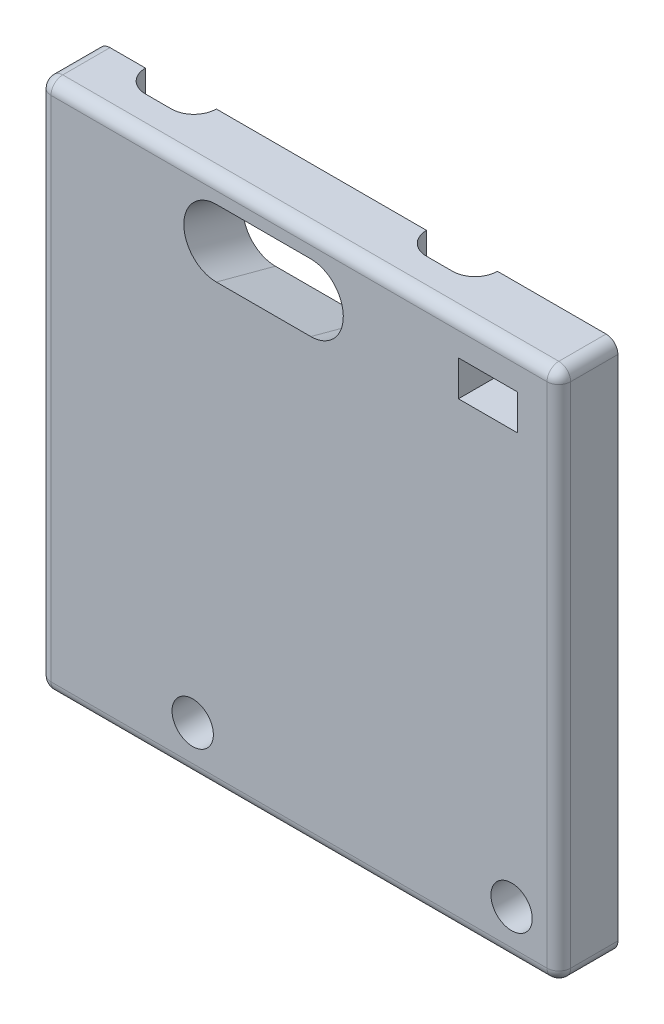
SolidWorks part; units mm, degrees
ref_plane "Front Plane" through (0, 0, 0) normal (0, 0, 1) x (1, 0, 0)
ref_plane "Top Plane" through (0, 0, 0) normal (0, 1, 0) x (1, 0, 0)
ref_plane "Right Plane" through (0, 0, 0) normal (1, 0, 0) x (0, 0, -1)
sketch "Sketch1" plane through (0, 0, 0) normal (0, 0, 1) x (1, 0, 0)
  line L1 (-22, 22.5) -> (22, 22.5)
  line L2 (-22, 22.5) -> (-22, -22.5)
  line L3 (-22, -22.5) -> (22, -22.5)
  line L4 (22, 22.5) -> (22, -22.5)
  line L5 (-22, 22.5) -> (22, -22.5) construction
  line L6 (-22, -22.5) -> (22, 22.5) construction
  point P0 (0, 0)
  dimension "D1" = 44
  dimension "D2" = 45
extrude "Base" add sketch "Sketch1" along normal blind 5
sketch "Sketch2" plane through (0, 22.5, 0) normal (0, 1, 0) x (1, 0, 0)
  line L0 (22, 0) -> (-22, 0) construction
  line L1 (-18, 0) -> (-12, 0)
  line L2 (0, 0) -> (0, -5) construction
  line L3 (22, -5) -> (-22, -5) construction
  line L5 (-16.1, -1.9) -> (-13.9, -1.9)
  line L6 (-18, 0) -> (-18, -5) construction
  line L7 (-3.1, 0) -> (-3.1, -5) construction
  line L8 (9.9, -1.9) -> (7.7, -1.9)
  line L9 (11.8, 0) -> (5.8, 0)
  arc A2 (-16.1, -1.9) -> (-18, 0) centre (-16.1, 0) cw
  arc A3 (-12, 0) -> (-13.9, -1.9) centre (-13.9, 0) cw
  arc A4 (9.9, -1.9) -> (11.8, 0) centre (9.9, 0) ccw
  arc A5 (5.8, 0) -> (7.7, -1.9) centre (7.7, 0) ccw
  point P0 (-15, 0)
  point P15 (-15, -1.9)
  dimension "D1" = 15
  dimension "D2" = 6
  dimension "D3" = 1.9
  dimension "D4" = 11.9
extrude "Wire Grooves" cut sketch "Sketch2" against normal through all
sketch "Sketch4" plane through (0, 0, 0) normal (0, 0, -1) x (-1, 0, 0)
  line L0 (0, 22.5) -> (0, -22.5) construction
  line L3 (-22, 16.5291) -> (22, 16.5291) construction
  line L4 (-22, -22.5) -> (-22, 22.5) construction
  line L5 (22, 22.5) -> (22, -22.5) construction
  line L6 (-22, 22.5) -> (-11.8, 22.5) construction
  line L7 (12, -22.5) -> (-5.8, -22.5) construction
  dimension "D1" = 5.9709
ref_plane "Screw Insertion Hole Reference" through (0, 1.1072, 4.1323) normal (0, -0.2588, -0.9659) x (-1, 0, 0)
sketch "Sketch3" plane through (0, 0.5961, 4.2692) normal (0, -0.2588, -0.9659) x (-1, 0, 0)
  line L0 (0, 0.5291) -> (0, 22.2625) construction
  line L1 (-1, 16.2925) -> (7, 16.2925) construction
  line L2 (-22, 22.2625) -> (-11.8, 22.2625) construction
  line L3 (-1, 19.0425) -> (7, 19.0425)
  line L4 (-1, 13.5425) -> (7, 13.5425)
  line L5 (-5.8, 22.2625) -> (12, 22.2625) construction
  arc A1 (-1, 19.0425) -> (-1, 13.5425) centre (-1, 16.2925) ccw
  arc A2 (7, 13.5425) -> (7, 19.0425) centre (7, 16.2925) ccw
  point P5 (3, 16.2925)
  point P14 (2.458, 16.2925)
  dimension "D1" = 5.97
  dimension "D2" = 2.75
  dimension "D3" = 8
  dimension "D4" = 3
extrude "Screw Insertion Hole" cut sketch "Sketch3" against normal through all both and the other way through all
sketch "Sketch5" plane through (0, 0, 0) normal (0, 0, -1) x (-1, 0, 0)
  line L1 (-22, 22.5) -> (-11.8, 22.5) construction
  line L3 (0, 22.5) -> (0, -22.5) construction
  line L7 (-18.5, 19.5) -> (-13.5, 19.5)
  line L8 (-18.5, 19.5) -> (-18.5, 16.5)
  line L9 (-18.5, 16.5) -> (-13.5, 16.5)
  line L10 (-13.5, 19.5) -> (-13.5, 16.5)
  line L11 (-18.5, 19.5) -> (-13.5, 16.5) construction
  line L12 (-18.5, 16.5) -> (-13.5, 19.5) construction
  line L16 (-22, 22.5) -> (-11.8, 22.5) construction
  line L20 (12, -22.5) -> (-5.8, -22.5) construction
  line L21 (-4, 22.5) -> (-4, -22.5) construction
  line L22 (-5.8, 22.5) -> (12, 22.5) construction
  line L23 (12, -22.5) -> (-5.8, -22.5) construction
  point P12 (-16, 18)
  dimension "D1" = 5
  dimension "D2" = 3
  dimension "D3" = 3
  dimension "D4" = 16
  dimension "D5" = 4
extrude "Zip Tie Slots" cut sketch "Sketch5" against normal through all
sketch "Sketch6" plane through (0, 0, 0) normal (0, 0, -1) x (-1, 0, 0)
  line L1 (-22, -22.5) -> (-22, 22.5) construction
  line L2 (12, -22.5) -> (-5.8, -22.5) construction
  line L4 (-4.5, 22.5) -> (-4.5, -22.5) construction
  line L6 (-22, 22.5) -> (-11.8, 22.5) construction
  circle A0 centre (-18, -18.5) radius 1.75
  circle A2 centre (9, -18.5) radius 1.75
  dimension "D1" = 3.5
  dimension "D2" = 4
  dimension "D3" = 4
  dimension "D4" = 4.5
extrude "Mount Clamping Holes" cut sketch "Sketch6" against normal through all
fillet "Edge Fillets" radius 1 8 edges at (-22, 0, 5) (22, 0, 5) (0, -22.5, 5) (0, 22.5, 5) (22, 22.5, 2.5) (22, -22.5, 2.5) (-22, -22.5, 2.5) (-22, 22.5, 2.5)
